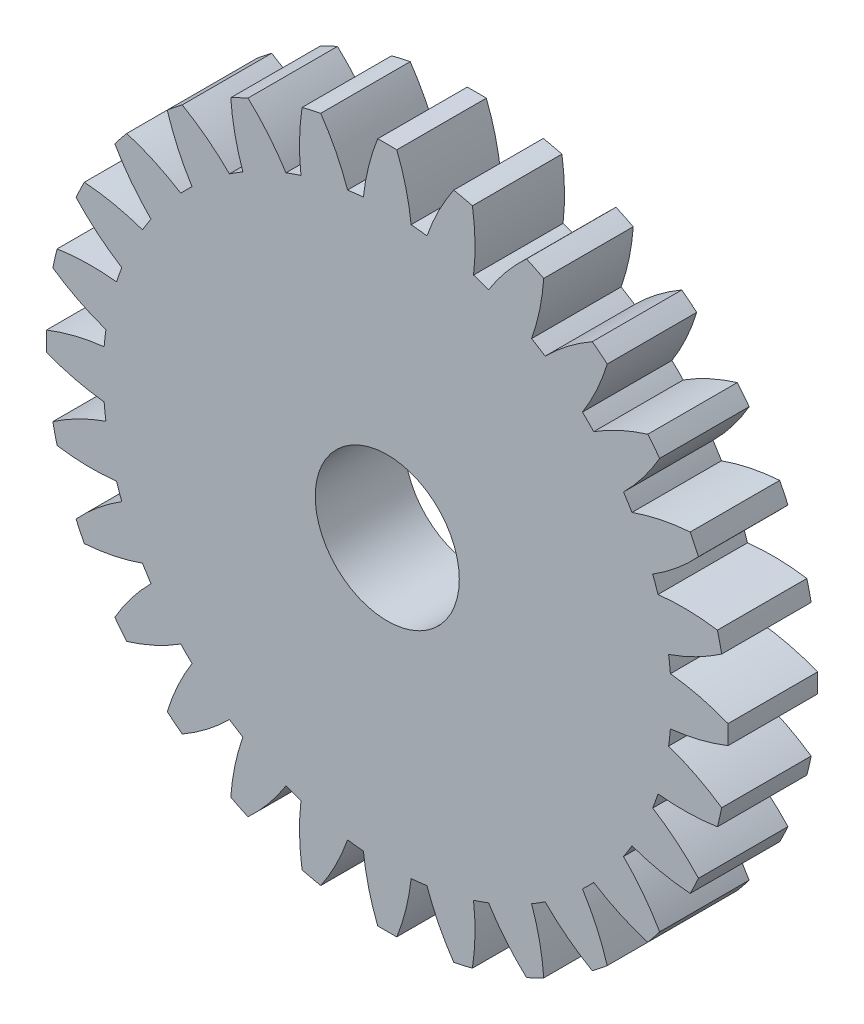
SolidWorks part; units mm, degrees
ref_plane "Front Plane" through (0, 0, 0) normal (0, 0, 1) x (1, 0, 0)
ref_plane "Top Plane" through (0, 0, 0) normal (0, 1, 0) x (1, 0, 0)
ref_plane "Right Plane" through (0, 0, 0) normal (1, 0, 0) x (0, 0, -1)
ref_plane "Plane1" through (0, 0, 5) normal (0, 0, 1) x (1, 0, 0)
sketch "Sketch1" plane through (0, 0, 5) normal (0, 0, 1) x (1, 0, 0)
  line L3 (0, 0) -> (-1.7774, 15.7752) construction
  arc A0 (-4.8209, 15.1253) -> (-5.6614, 14.8312) centre (0, 0) ccw
  arc A1 (-5.6614, 14.8312) -> (-7.7809, 17.3885) centre (-16.2618, 8.2026) ccw
  arc A2 (-7.7809, 17.3885) -> (-8.7436, 16.9249) centre (0, 0) ccw
  arc A3 (-8.7436, 16.9249) -> (-8.0657, 13.6733) centre (3.7261, 17.8282) ccw
  arc A4 (-8.0657, 13.6733) -> (-8.8197, 13.1996) centre (0, 0) ccw
  arc A5 (-8.8197, 13.1996) -> (-11.4551, 15.2211) centre (-17.6794, 4.3783) ccw
  arc A6 (-11.4551, 15.2211) -> (-12.2905, 14.5549) centre (0, 0) ccw
  arc A7 (-12.2905, 14.5549) -> (-10.9061, 11.5357) centre (-0.3345, 18.2104) ccw
  arc A8 (-10.9061, 11.5357) -> (-11.5357, 10.9061) centre (0, 0) ccw
  arc A9 (-11.5357, 10.9061) -> (-14.5549, 12.2905) centre (-18.2104, 0.3345) ccw
  arc A10 (-14.5549, 12.2905) -> (-15.2211, 11.4551) centre (0, 0) ccw
  arc A11 (-15.2211, 11.4551) -> (-13.1996, 8.8197) centre (-4.3783, 17.6794) ccw
  arc A12 (-13.1996, 8.8197) -> (-13.6733, 8.0657) centre (0, 0) ccw
  arc A13 (-13.6733, 8.0657) -> (-16.9249, 8.7436) centre (-17.8282, -3.7261) ccw
  arc A14 (-16.9249, 8.7436) -> (-17.3885, 7.7809) centre (0, 0) ccw
  arc A15 (-17.3885, 7.7809) -> (-14.8312, 5.6614) centre (-8.2026, 16.2618) ccw
  arc A16 (-14.8312, 5.6614) -> (-15.1253, 4.8209) centre (0, 0) ccw
  arc A17 (-15.1253, 4.8209) -> (-18.4462, 4.7582) centre (-16.5521, -7.5998) ccw
  arc A18 (-18.4462, 4.7582) -> (-18.684, 3.7165) centre (0, 0) ccw
  arc A19 (-18.684, 3.7165) -> (-15.7191, 2.2192) centre (-11.6155, 14.0289) ccw
  arc A20 (-15.7191, 2.2192) -> (-15.8188, 1.3343) centre (0, 0) ccw
  arc A21 (-15.8188, 1.3343) -> (-19.0425, 0.5343) centre (-14.446, -11.0924) ccw
  arc A22 (-19.0425, 0.5343) -> (-19.0425, -0.5343) centre (0, 0) ccw
  arc A23 (-19.0425, -0.5343) -> (-15.8188, -1.3343) centre (-14.446, 11.0924) ccw
  arc A24 (-15.8188, -1.3343) -> (-15.7191, -2.2192) centre (0, 0) ccw
  arc A25 (-15.7191, -2.2192) -> (-18.684, -3.7165) centre (-11.6155, -14.0289) ccw
  arc A26 (-18.684, -3.7165) -> (-18.4462, -4.7582) centre (0, 0) ccw
  arc A27 (-18.4462, -4.7582) -> (-15.1253, -4.8209) centre (-16.5521, 7.5998) ccw
  arc A28 (-15.1253, -4.8209) -> (-14.8312, -5.6614) centre (0, 0) ccw
  arc A29 (-14.8312, -5.6614) -> (-17.3885, -7.7809) centre (-8.2026, -16.2618) ccw
  arc A30 (-17.3885, -7.7809) -> (-16.9249, -8.7436) centre (0, 0) ccw
  arc A31 (-16.9249, -8.7436) -> (-13.6733, -8.0657) centre (-17.8282, 3.7261) ccw
  arc A32 (-13.6733, -8.0657) -> (-13.1996, -8.8197) centre (0, 0) ccw
  arc A33 (-13.1996, -8.8197) -> (-15.2211, -11.4551) centre (-4.3783, -17.6794) ccw
  arc A34 (-15.2211, -11.4551) -> (-14.5549, -12.2905) centre (0, 0) ccw
  arc A35 (-14.5549, -12.2905) -> (-11.5357, -10.9061) centre (-18.2104, -0.3345) ccw
  arc A36 (-11.5357, -10.9061) -> (-10.9061, -11.5357) centre (0, 0) ccw
  arc A37 (-10.9061, -11.5357) -> (-12.2905, -14.5549) centre (-0.3345, -18.2104) ccw
  arc A38 (-12.2905, -14.5549) -> (-11.4551, -15.2211) centre (0, 0) ccw
  arc A39 (-11.4551, -15.2211) -> (-8.8197, -13.1996) centre (-17.6794, -4.3783) ccw
  arc A40 (-8.8197, -13.1996) -> (-8.0657, -13.6733) centre (0, 0) ccw
  arc A41 (-8.0657, -13.6733) -> (-8.7436, -16.9249) centre (3.7261, -17.8282) ccw
  arc A42 (-8.7436, -16.9249) -> (-7.7809, -17.3885) centre (0, 0) ccw
  arc A43 (-7.7809, -17.3885) -> (-5.6614, -14.8312) centre (-16.2618, -8.2026) ccw
  arc A44 (-5.6614, -14.8312) -> (-4.8209, -15.1253) centre (0, 0) ccw
  arc A45 (-4.8209, -15.1253) -> (-4.7582, -18.4462) centre (7.5998, -16.5521) ccw
  arc A46 (-4.7582, -18.4462) -> (-3.7165, -18.684) centre (0, 0) ccw
  arc A47 (-3.7165, -18.684) -> (-2.2192, -15.7191) centre (-14.0289, -11.6155) ccw
  arc A48 (-2.2192, -15.7191) -> (-1.3343, -15.8188) centre (0, 0) ccw
  arc A49 (-1.3343, -15.8188) -> (-0.5343, -19.0425) centre (11.0924, -14.446) ccw
  arc A50 (-0.5343, -19.0425) -> (0.5343, -19.0425) centre (0, 0) ccw
  arc A51 (0.5343, -19.0425) -> (1.3343, -15.8188) centre (-11.0924, -14.446) ccw
  arc A52 (1.3343, -15.8188) -> (2.2192, -15.7191) centre (0, 0) ccw
  arc A53 (2.2192, -15.7191) -> (3.7165, -18.684) centre (14.0289, -11.6155) ccw
  arc A54 (3.7165, -18.684) -> (4.7582, -18.4462) centre (0, 0) ccw
  arc A55 (4.7582, -18.4462) -> (4.8209, -15.1253) centre (-7.5998, -16.5521) ccw
  arc A56 (4.8209, -15.1253) -> (5.6614, -14.8312) centre (0, 0) ccw
  arc A57 (5.6614, -14.8312) -> (7.7809, -17.3885) centre (16.2618, -8.2026) ccw
  arc A58 (7.7809, -17.3885) -> (8.7436, -16.9249) centre (0, 0) ccw
  arc A59 (8.7436, -16.9249) -> (8.0657, -13.6733) centre (-3.7261, -17.8282) ccw
  arc A60 (8.0657, -13.6733) -> (8.8197, -13.1996) centre (0, 0) ccw
  arc A61 (8.8197, -13.1996) -> (11.4551, -15.2211) centre (17.6794, -4.3783) ccw
  arc A62 (11.4551, -15.2211) -> (12.2905, -14.5549) centre (0, 0) ccw
  arc A63 (12.2905, -14.5549) -> (10.9061, -11.5357) centre (0.3345, -18.2104) ccw
  arc A64 (10.9061, -11.5357) -> (11.5357, -10.9061) centre (0, 0) ccw
  arc A65 (11.5357, -10.9061) -> (14.5549, -12.2905) centre (18.2104, -0.3345) ccw
  arc A66 (14.5549, -12.2905) -> (15.2211, -11.4551) centre (0, 0) ccw
  arc A67 (15.2211, -11.4551) -> (13.1996, -8.8197) centre (4.3783, -17.6794) ccw
  arc A68 (13.1996, -8.8197) -> (13.6733, -8.0657) centre (0, 0) ccw
  arc A69 (13.6733, -8.0657) -> (16.9249, -8.7436) centre (17.8282, 3.7261) ccw
  arc A70 (16.9249, -8.7436) -> (17.3885, -7.7809) centre (0, 0) ccw
  arc A71 (17.3885, -7.7809) -> (14.8312, -5.6614) centre (8.2026, -16.2618) ccw
  arc A72 (14.8312, -5.6614) -> (15.1253, -4.8209) centre (0, 0) ccw
  arc A73 (15.1253, -4.8209) -> (18.4462, -4.7582) centre (16.5521, 7.5998) ccw
  arc A74 (18.4462, -4.7582) -> (18.684, -3.7165) centre (0, 0) ccw
  arc A75 (18.684, -3.7165) -> (15.7191, -2.2192) centre (11.6155, -14.0289) ccw
  arc A76 (15.7191, -2.2192) -> (15.8188, -1.3343) centre (0, 0) ccw
  arc A77 (15.8188, -1.3343) -> (19.0425, -0.5343) centre (14.446, 11.0924) ccw
  arc A78 (19.0425, -0.5343) -> (19.0425, 0.5343) centre (0, 0) ccw
  arc A79 (19.0425, 0.5343) -> (15.8188, 1.3343) centre (14.446, -11.0924) ccw
  arc A80 (15.8188, 1.3343) -> (15.7191, 2.2192) centre (0, 0) ccw
  arc A81 (15.7191, 2.2192) -> (18.684, 3.7165) centre (11.6155, 14.0289) ccw
  arc A82 (18.684, 3.7165) -> (18.4462, 4.7582) centre (0, 0) ccw
  arc A83 (18.4462, 4.7582) -> (15.1253, 4.8209) centre (16.5521, -7.5998) ccw
  arc A84 (15.1253, 4.8209) -> (14.8312, 5.6614) centre (0, 0) ccw
  arc A85 (14.8312, 5.6614) -> (17.3885, 7.7809) centre (8.2026, 16.2618) ccw
  arc A86 (17.3885, 7.7809) -> (16.9249, 8.7436) centre (0, 0) ccw
  arc A87 (16.9249, 8.7436) -> (13.6733, 8.0657) centre (17.8282, -3.7261) ccw
  arc A88 (13.6733, 8.0657) -> (13.1996, 8.8197) centre (0, 0) ccw
  arc A89 (13.1996, 8.8197) -> (15.2211, 11.4551) centre (4.3783, 17.6794) ccw
  arc A90 (15.2211, 11.4551) -> (14.5549, 12.2905) centre (0, 0) ccw
  arc A91 (14.5549, 12.2905) -> (11.5357, 10.9061) centre (18.2104, 0.3345) ccw
  arc A92 (11.5357, 10.9061) -> (10.9061, 11.5357) centre (0, 0) ccw
  arc A93 (10.9061, 11.5357) -> (12.2905, 14.5549) centre (0.3345, 18.2104) ccw
  arc A94 (12.2905, 14.5549) -> (11.4551, 15.2211) centre (0, 0) ccw
  arc A95 (11.4551, 15.2211) -> (8.8197, 13.1996) centre (17.6794, 4.3783) ccw
  arc A96 (8.8197, 13.1996) -> (8.0657, 13.6733) centre (0, 0) ccw
  arc A97 (8.0657, 13.6733) -> (8.7436, 16.9249) centre (-3.7261, 17.8282) ccw
  arc A98 (8.7436, 16.9249) -> (7.7809, 17.3885) centre (0, 0) ccw
  arc A99 (7.7809, 17.3885) -> (5.6614, 14.8312) centre (16.2618, 8.2026) ccw
  arc A100 (5.6614, 14.8312) -> (4.8209, 15.1253) centre (0, 0) ccw
  arc A101 (4.8209, 15.1253) -> (4.7582, 18.4462) centre (-7.5998, 16.5521) ccw
  arc A102 (4.7582, 18.4462) -> (3.7165, 18.684) centre (0, 0) ccw
  arc A103 (3.7165, 18.684) -> (2.2192, 15.7191) centre (14.0289, 11.6155) ccw
  arc A104 (2.2192, 15.7191) -> (1.3343, 15.8188) centre (0, 0) ccw
  arc A105 (1.3343, 15.8188) -> (0.5343, 19.0425) centre (-11.0924, 14.446) ccw
  arc A106 (0.5343, 19.0425) -> (-0.5343, 19.0425) centre (0, 0) ccw
  arc A107 (-0.5343, 19.0425) -> (-1.3343, 15.8188) centre (11.0924, 14.446) ccw
  arc A108 (-1.3343, 15.8188) -> (-2.2192, 15.7191) centre (0, 0) ccw
  arc A109 (-2.2192, 15.7191) -> (-3.7165, 18.684) centre (-14.0289, 11.6155) ccw
  arc A110 (-3.7165, 18.684) -> (-4.7582, 18.4462) centre (0, 0) ccw
  arc A111 (-4.7582, 18.4462) -> (-4.8209, 15.1253) centre (7.5998, 16.5521) ccw
  circle A112 centre (0, 0) radius 4.025
  dimension "D2" = 8.05
  dimension "D1" = 19.05
extrude "Boss-Extrude1" add sketch "Sketch1" against normal blind 5
ref_axis "Axis1" through (0, 0, 0) along (0, 0, 1)
sketch "Sketch2" [suppressed] plane through (0, 0, 5) normal (0, 0, 1) x (1, 0, 0)
  line L0 (0, 0) -> (0, 19.05) construction
  line L1 (0, 0) -> (14.9841, 5.2432) construction
  line L2 (0, 0) -> (5.2432, -14.9841) construction
  line L3 (0, 0) -> (0, -19.05) construction
  arc A0 (0.5343, 19.0425) -> (-0.5343, 19.0425) centre (0, 0) ccw construction
  arc A1 (15.1253, 4.8209) -> (14.8312, 5.6614) centre (0, 0) ccw construction
  arc A2 (4.8209, -15.1253) -> (5.6614, -14.8312) centre (0, 0) ccw construction
  arc A3 (-0.5343, -19.0425) -> (0.5343, -19.0425) centre (0, 0) ccw construction
